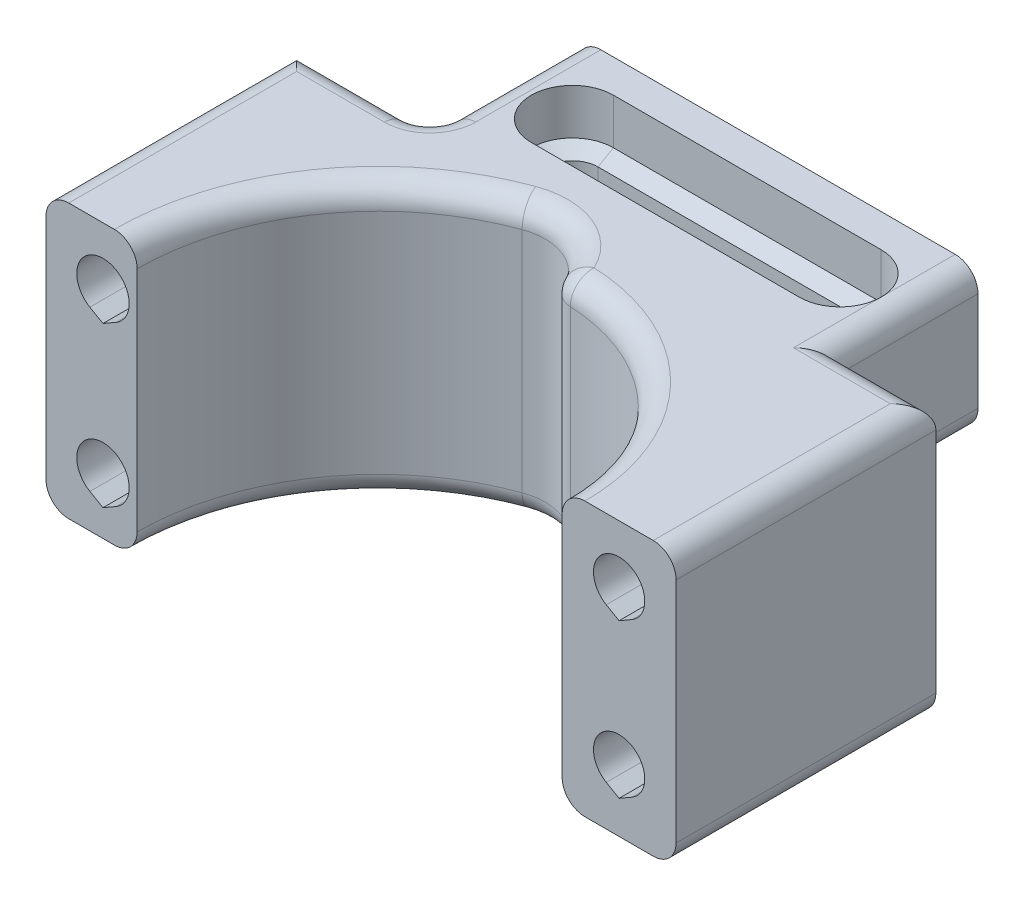
SolidWorks part; units mm, degrees
ref_plane "Ebene vorne" through (0, 0, 0) normal (0, 0, 1) x (1, 0, 0)
ref_plane "Ebene oben" through (0, 0, 0) normal (0, 1, 0) x (1, 0, 0)
ref_plane "Ebene rechts" through (0, 0, 0) normal (1, 0, 0) x (0, 0, -1)
sketch "Skizze1" plane through (0, 0, 0) normal (0, 1, 0) x (1, 0, 0)
  line L0 (-29.15, 0) -> (-16.15, 0)
  line L1 (-29.15, 0) -> (-29.15, 22)
  line L2 (-29.15, 22) -> (-17.45, 22)
  line L3 (-17.45, 22) -> (-17.45, 35)
  line L5 (26.15, 22.8) -> (26.15, 0)
  line L6 (26.15, 0) -> (16.15, 0)
  line L7 (-16.15, 0) -> (16.15, 0) construction
  line L8 (-7.2337, 19.8745) -> (0, 0) construction
  line L9 (17.65, 35) -> (17.65, 22.8)
  line L10 (17.65, 22.8) -> (26.15, 22.8)
  line L11 (17.65, 35) -> (-17.45, 35)
  circle A0 centre (0, 0) radius 16.15
  arc A1 (-21.15, 0) -> (-7.2337, 19.8745) centre (0, 0) cw
  arc A2 (-7.2337, 19.8745) -> (-0.6171, 16.1382) centre (-5.5236, 15.176) cw
  dimension "D1" = 32.3
  dimension "D8" = 5
  dimension "D2" = 13
  dimension "D3" = 13
  dimension "D4" = 22
  dimension "D5" = 11.7
  dimension "D6" = 10
  dimension "D7" = 70
  dimension "D9" = 8.5
  dimension "D10" = 12.2
extrude "Aufsatz-Linear austragen1" add sketch "Skizze1" along normal blind 24 contours A0 L6 L5 L3 L2 L1 L0 region at (0.0878, 0, -19.5638)
fillet "Verrundung1" radius 2 1 edges at (-17.45, 12, -22)
sketch "Skizze6" plane through (0, 0, 0) normal (0, 0, 1) x (1, 0, 0)
  line L1 (-29.15, 24) -> (-29.15, 0) construction
  line L3 (-29.15, 24) -> (-21.15, 24) construction
  line L4 (-24.15, 19) -> (-24.15, 16.3442) construction
  line L5 (-29.15, 0) -> (-21.15, 0) construction
  line L6 (-24.15, 16.3442) -> (-23, 17.0081)
  line L7 (-24.15, 16.3442) -> (-25.3, 17.0081)
  line L8 (-24.15, 5) -> (-24.15, 2.3442) construction
  line L9 (-24.15, 2.3442) -> (-23, 3.0081)
  line L10 (-24.15, 2.3442) -> (-25.3, 3.0081)
  circle A0 centre (-24.15, 19) radius 2.3
  circle A1 centre (-24.15, 5) radius 2.3
  dimension "D2" = 4.6
  dimension "D5" = 4.6
  dimension "D1" = 5
  dimension "D3" = 5
  dimension "D4" = 60
  dimension "D6" = 5
  dimension "D7" = 5
  dimension "D8" = 60
extrude "Schnitt-Linear austragen2" cut sketch "Skizze6" against normal blind 100 contours A0 | A1 | A0 L7 L6 | A1 L10 L9 region at (-24.15, 16.6228, 0) region at (-24.15, 19, 0) region at (-24.15, 2.6228, 0) region at (-24.15, 5, 0)
sketch "Skizze7" plane through (26.15, 0, 0) normal (1, 0, 0) x (0, 0, -1)
  line L1 (35, 0) -> (22.8, 0)
  line L2 (35, 0) -> (35, 11.3)
  line L3 (35, 11.3) -> (22.8, 11.3)
  line L4 (22.8, 0) -> (22.8, 11.3)
  dimension "D1" = 12.2
  dimension "D2" = 11.3
extrude "Schnitt-Linear austragen3" cut sketch "Skizze7" against normal through all
sketch "Skizze8" plane through (0, 0, -22.8) normal (0, 0, -1) x (-1, 0, 0)
  line L0 (-26.15, 24) -> (-26.15, 0) construction
  line L1 (17.85, 0) -> (-26.15, 0) construction
  line L2 (-21.15, 5.5) -> (-21.15, 2.9019) construction
  line L3 (-21.15, 2.9019) -> (-20.025, 3.5514)
  line L4 (-22.275, 3.5514) -> (-21.15, 2.9019)
  line L5 (-26.15, 24) -> (-26.15, 0) construction
  line L7 (-17.65, 24) -> (-26.15, 24) construction
  line L8 (-21.15, 19) -> (-21.15, 16.4019) construction
  line L9 (-21.15, 16.4019) -> (-20.025, 17.0514)
  line L10 (-21.15, 16.4019) -> (-22.275, 17.0514)
  circle A0 centre (-21.15, 5.5) radius 2.25
  circle A1 centre (-21.15, 19) radius 2.25
  dimension "D1" = 4.5
  dimension "D5" = 4.5
  dimension "D2" = 5
  dimension "D3" = 5.5
  dimension "D4" = 60
  dimension "D6" = 5
  dimension "D7" = 5
  dimension "D8" = 60
extrude "Schnitt-Linear austragen4" cut sketch "Skizze8" against normal blind 25 contours A0 | A1 | A1 L10 L9 | A0 L4 L3 region at (21.15, 3.1745, -22.8) region at (21.15, 5.5, -22.8) region at (21.15, 16.6745, -22.8) region at (21.15, 19, -22.8)
sketch "Skizze10" plane through (0, 11.3, 0) normal (0, -1, 0) x (1, 0, 0)
  line L0 (-11.45, -28.5) -> (12.05, -28.5) construction
  line L1 (-11.45, -26.25) -> (12.05, -26.25)
  line L2 (-11.45, -30.75) -> (12.05, -30.75)
  line L3 (-17.45, -24) -> (-17.45, -35) construction
  line L6 (-17.45, -35) -> (17.65, -35) construction
  arc A0 (-11.45, -26.25) -> (-11.45, -30.75) centre (-11.45, -28.5) ccw
  arc A1 (12.05, -30.75) -> (12.05, -26.25) centre (12.05, -28.5) ccw
  point P2 (0.3, -28.5)
  dimension "D2" = 2.25
  dimension "D1" = 6
  dimension "D3" = 23.5
  dimension "D4" = 6.5
extrude "Schnitt-Linear austragen5" cut sketch "Skizze10" against normal through all
fillet "Verrundung2" radius 2 19 edges at (-17.5526, 11.3, -23.3675) (-17.3251, 24, -12.1311) (-17.3251, 0, -12.1311) (-29.15, 24, -11) (26.15, 24, -11.4) (-17.45, 11.3, -29.5) (-29.15, 0, -11) (26.15, 0, -11.4) (-3.0651, 24, -19.5299) (-3.0651, 0, -19.5299) (11.1995, 24, -11.6359) (11.1995, 0, -11.6359) (-0.6171, 12, -16.1382) (-24.3, 24, -22) (-18.0358, 24, -22.5858) (-17.45, 24, -29.5) (21.9, 24, -22.8) (17.65, 24, -28.9) (17.65, 11.3, -28.9)
ref_plane "Ebene1" through (-11.45, 0, 0) normal (1, 0, 0) x (0, 0, -1)
ref_plane "Ebene2" through (0.3, 0, 0) normal (-1, 0, 0) x (0, 0, 1)
sketch "Skizze12" plane through (-11.45, 0, 0) normal (1, 0, 0) x (0, 0, -1)
  line L0 (28.5, 24) -> (28.5, 19.2206) construction
  line L1 (30.75, 24) -> (26.25, 24) construction
  line L2 (24.9, 24) -> (24.9, 20)
  line L3 (35, 24) -> (24, 24) construction
  line L4 (24.9, 20) -> (26.25, 19.2206)
  line L5 (26.25, 19.2206) -> (30.75, 19.2206)
  line L6 (30.75, 19.2206) -> (32.1, 20)
  line L7 (32.1, 20) -> (32.1, 24)
  line L8 (32.1, 24) -> (24.9, 24)
  line L9 (30.75, 24) -> (30.75, 11.3) construction
  line L10 (26.25, 24) -> (26.25, 11.3) construction
  dimension "D1" = 4
  dimension "D2" = 30
  dimension "D3" = 7.2
extrude "Schnitt-Linear austragen6" cut sketch "Skizze12" along normal up to vertex (23.5 mm away) up to point (12.05, 24, -30.75)
revolve "Schnitt-Rotation1" cut sketch "Skizze12<3>" angle 360 about L0 region at (-11.45, 21.6775, -30.2574)
sketch "Skizze12<3>" plane through (-11.45, 0, 0) normal (1, 0, 0) x (0, 0, -1) same geometry as "Skizze12"
mirror "Spiegeln1" about plane through (0.3, 0, 0) normal (-1, 0, 0) of "Schnitt-Rotation1"
